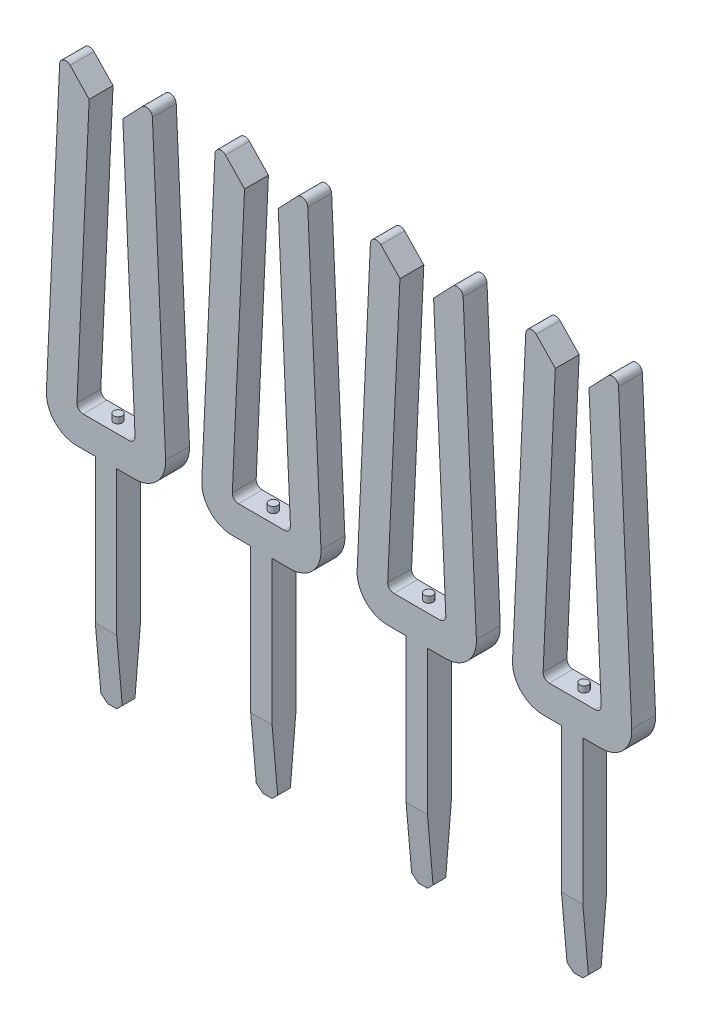
SolidWorks part; units mm, degrees
other "Шпилька"
ref_plane "Front Plane" through (0, 0, 0) normal (0, 0, 1) x (1, 0, 0)
ref_plane "Top Plane" through (0, 0, 0) normal (0, 1, 0) x (1, 0, 0)
ref_plane "Right Plane" through (0, 0, 0) normal (1, 0, 0) x (0, 0, -1)
sketch "Эскиз-Шпилька" plane through (0, 0, 0) normal (0, 0, 1) x (1, 0, 0)
  line L0 (-0.2751, 4.5045) -> (-0.586, 4.8299)
  line L1 (-0.7582, 4.7653) -> (-0.9745, 0.0228)
  line L2 (-0.475, -0.5) -> (-0.175, -0.5)
  line L3 (-0.175, -0.5) -> (-0.175, -3.9)
  line L4 (-0.175, -3.9) -> (-0.075, -4)
  line L5 (0, 4.5045) -> (0, -4) construction
  line L6 (-0.375, 0) -> (0.375, 0)
  line L7 (-0.4749, 0.1045) -> (-0.2751, 4.5045)
  line L8 (0.4749, 0.1045) -> (0.2751, 4.5045)
  line L9 (0.175, -3.9) -> (0.075, -4)
  line L10 (0.175, -0.5) -> (0.175, -3.9)
  line L11 (0.475, -0.5) -> (0.175, -0.5)
  line L12 (0.7582, 4.7653) -> (0.9745, 0.0228)
  line L13 (0.2751, 4.5045) -> (0.586, 4.8299)
  line L14 (-0.075, -4) -> (0.075, -4)
  arc A0 (-0.9745, 0.0228) -> (-0.475, -0.5) centre (-0.475, 0) ccw
  arc A1 (-0.4749, 0.1045) -> (-0.375, 0) centre (-0.375, 0.1) ccw
  arc A2 (-0.586, 4.8299) -> (-0.7582, 4.7653) centre (-0.6583, 4.7608) ccw
  arc A3 (0.586, 4.8299) -> (0.7582, 4.7653) centre (0.6583, 4.7608) cw
  arc A4 (0.4749, 0.1045) -> (0.375, 0) centre (0.375, 0.1) cw
  arc A5 (0.9745, 0.0228) -> (0.475, -0.5) centre (0.475, 0) cw
  point P26 (0, 0)
  dimension "D1" = 2.6
  dimension "D2" = 0.1
  dimension "D6" = 0.1
  dimension "D8" = 0.5
  dimension "D3" = 0.45
  dimension "D4" = 133.7
  dimension "D5" = 4.4
  dimension "D7" = 0.375
  dimension "D9" = 0.3
  dimension "D10" = 3.5
  dimension "D11" = 0.1
  dimension "D12" = 0.1
  dimension "D13" = 0.35
  dimension "D14" = 0.5
extrude "Бобышка-Шпилька" add sketch "Эскиз-Шпилька" along normal blind 0.195 and the other way blind 0.195
chamfer "Фаска1" distance 0.1 angle 85 1 edges at (0, -4, 0.195) first distance on face at (0, -4, 0)
chamfer "Фаска2" distance 0.1 angle 85 1 edges at (0, -4, -0.195) first distance on face at (0, -4, -0.05)
sketch "Esboço1" plane through (0, 0, 0) normal (0, 1, 0) x (1, 0, 0)
  circle A0 centre (0, 0) radius 0.0715
extrude "Ressalto-extrusão1" add sketch "Esboço1" along normal blind 0.1
ref_axis "Eixo1" through (0, 4.9224, 0) along (0, -1, 0)
pattern_linear "Линейный массив1" count 4 spacing 2.54 along (-1, 0, 0) of "Бобышка-Шпилька"
